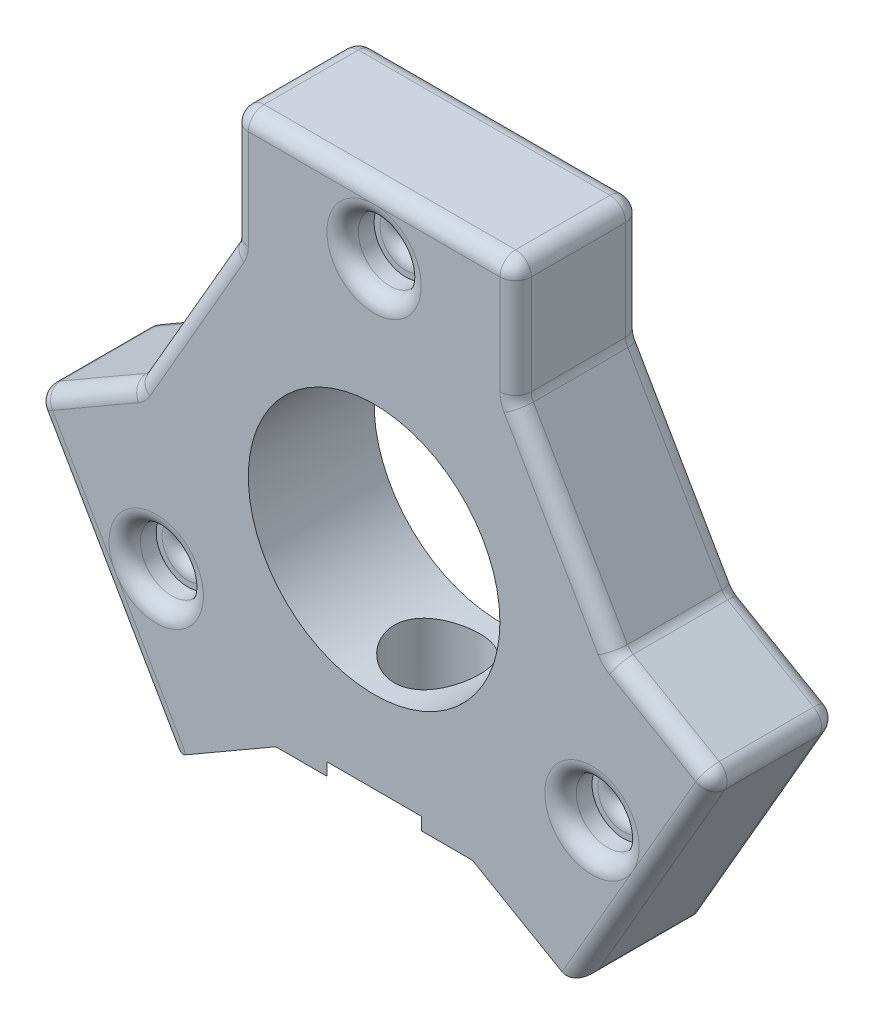
SolidWorks part; units mm, degrees
material "Polyetheretherketone (PEEK)"
ref_plane "Front Plane" through (0, 0, 0) normal (0, 0, 1) x (1, 0, 0)
ref_plane "Top Plane" through (0, 0, 0) normal (0, 1, 0) x (1, 0, 0)
ref_plane "Right Plane" through (0, 0, 0) normal (1, 0, 0) x (0, 0, -1)
sketch "Sketch3" plane through (0, 0, 0) normal (0, 0, 1) x (1, 0, 0)
  line L0 (0, 0) -> (9.6237, 5.5563) construction
  line L1 (0, 0) -> (0, 9.525) construction
  line L2 (7.1437, 9.8517) -> (7.1437, 15.875)
  line L3 (7.1437, 9.8517) -> (12.1037, 1.2608)
  line L4 (0, 0) -> (10.9985, -6.35) construction
  line L5 (0, 0) -> (-10.9985, -6.35) construction
  line L6 (0, 0) -> (0, 12.7) construction
  line L7 (10.9985, -6.35) -> (-10.9985, -6.35) construction
  line L8 (-10.9985, -6.35) -> (0, 12.7) construction
  line L9 (0, 15.875) -> (7.1437, 15.875)
  line L10 (13.7482, -7.9375) -> (17.32, -1.7508)
  line L11 (12.1037, 1.2608) -> (17.32, -1.7508)
  line L12 (0, 0) -> (0, -9.5744) construction
  line L13 (0, 0) -> (13.7482, -7.9375) construction
  line L14 (0, 6.35) -> (9.1654, 6.35) construction
  line L15 (13.7482, -7.9375) -> (10.1763, -14.1242)
  line L16 (4.9599, -11.1125) -> (-4.9599, -11.1125)
  line L17 (-4.9599, -11.1125) -> (-10.1763, -14.1242)
  line L18 (0, 12.7) -> (10.9985, -6.35) construction
  line L19 (3.9688, 9.525) -> (3.9688, 2.2914) construction
  line L20 (-13.7482, -7.9375) -> (-10.1763, -14.1242)
  line L21 (4.9599, -11.1125) -> (10.1763, -14.1242)
  line L22 (0, 12.7) -> (0, 15.875) construction
  line L23 (-13.7482, -7.9375) -> (-17.32, -1.7508)
  line L24 (-12.1037, 1.2608) -> (-7.1437, 9.8517)
  line L25 (-7.1437, 9.8517) -> (-7.1437, 15.875)
  line L26 (0, 15.875) -> (-7.1437, 15.875)
  line L27 (-12.1037, 1.2608) -> (-17.32, -1.7508)
  circle A0 centre (0, 0) radius 6.35
  circle A1 centre (-10.9985, -6.35) radius 0.5
  circle A2 centre (10.9985, -6.35) radius 0.5
  circle A3 centre (0, 12.7) radius 0.5
  dimension "D1" = 12.7
  dimension "D5" = 120
  dimension "D7" = 1
  dimension "D2" = 12.7
  dimension "D3" = 3.9688
  dimension "D4" = 120
  dimension "D6" = 15.875
  dimension "D8" = 3.175
  dimension "D9" = 4.7625
  dimension "D10" = 3
extrude "Boss-Extrude2" add sketch "Sketch3" along normal blind 6.35
sketch "Sketch12" plane through (0, 0, 6.35) normal (0, 0, 1) x (1, 0, 0)
  circle A1 centre (0, 12.7) radius 1.5875
  circle A2 centre (10.9985, -6.35) radius 1.5875
  circle A3 centre (-10.9985, -6.35) radius 1.5875
  dimension "D1" = 3.175
extrude "Cut-Extrude4" cut sketch "Sketch12" against normal blind 1.5875
sketch "Sketch13" plane through (0, 0, 0) normal (0, 0, -1) x (-1, 0, 0)
  circle A0 centre (-10.9985, -6.35) radius 1.5875
  circle A1 centre (0, 12.7) radius 1.5875
  circle A2 centre (10.9985, -6.35) radius 1.5875
  circle A3 centre (0, 12.7) radius 1.5875 construction
extrude "Cut-Extrude5" cut sketch "Sketch13" against normal blind 1.5875
fillet "Fillet1" radius 0.7937 12 edges at (11.4985, -6.35, 4.7625) (10.4985, -6.35, 1.5875) (-0.5, 12.7, 1.5875) (0.5, 12.7, 4.7625) (-11.4985, -6.35, 1.5875) (-10.4985, -6.35, 4.7625) (1.5875, 12.7, 6.35) (12.586, -6.35, 6.35) (-9.411, -6.35, 6.35) (-12.586, -6.35, 0) (9.411, -6.35, 0) (-1.5875, 12.7, 0)
fillet "Fillet2" radius 0.7937 28 edges at (14.7118, -0.245, 6.35) (14.7118, -0.245, 0) (7.1437, 12.8633, 6.35) (7.1437, 12.8633, 0) (-7.1437, 12.8633, 6.35) (-7.1437, 12.8633, 0) (-14.7118, -0.245, 6.35) (-14.7118, -0.245, 0) (10.1763, -14.1242, 3.175) (13.7482, -7.9375, 6.35) (17.32, -1.7508, 3.175) (13.7482, -7.9375, 0) (-17.32, -1.7508, 3.175) (-13.7482, -7.9375, 6.35) (-10.1763, -14.1242, 3.175) (-13.7482, -7.9375, 0) (0, 15.875, 0) (0, 15.875, 6.35) (12.1037, 1.2608, 3.175) (9.6237, 5.5563, 6.35) (7.1437, 9.8517, 3.175) (9.6237, 5.5563, 0) (-7.1437, 9.8517, 3.175) (-9.6237, 5.5562, 6.35) (-12.1037, 1.2608, 3.175) (-9.6237, 5.5562, 0) (7.1437, 15.875, 3.175) (-7.1437, 15.875, 3.175)
hole_wizard "CBORE for #8 Socket Head Cap Screw1" positions "Sketch15" profile "Sketch14" counterbore size "#8" standard "Ansi Inch" end condition up to next
sketch "Sketch15" plane through (0, -11.1125, 0) normal (0, -1, 0) x (1, 0, 0)
  line L0 (-4.9599, 3.175) -> (4.9599, 3.175) construction
  line L1 (-4.9599, 6.35) -> (-4.9599, 0) construction
  line L2 (4.9599, 6.35) -> (4.9599, 0) construction
  point P0 (0, 3.175)
sketch "Sketch14" plane through (0, -11.1125, 3.175) normal (1, 0, 0) x (0, 0, -1)
  line L0 (0, 0) -> (0, 4.7625)
  line L1 (0, 4.7625) -> (2.1526, 4.7625)
  line L3 (2.1526, 4.7625) -> (2.1526, 0.635)
  line L4 (2.1526, 0.635) -> (3.9688, 0.635)
  line L5 (3.9688, 0.635) -> (3.9688, 0)
  line L7 (3.9688, 0) -> (0, 0)
  line L11 (0, -6.35) -> (0, 107.95) construction
  dimension "Thru Hole Dia." = 4.3053
  dimension "Thru Hole Depth" = 4.7625
  dimension "C'Bore Dia." = 7.9375
  dimension "C'Bore Depth" = 0.635
sketch "Sketch16" plane through (0, -10.4775, 0) normal (0, -1, 0) x (1, 0, 0)
  circle A0 centre (0, 3.175) radius 3.9688
  arc A1 (-2.3812, 6.35) -> (-2.3812, 0) centre (0, 3.175) ccw construction
extrude "Cut-Extrude6" [suppressed] cut sketch "Sketch16" along normal blind 2.54
